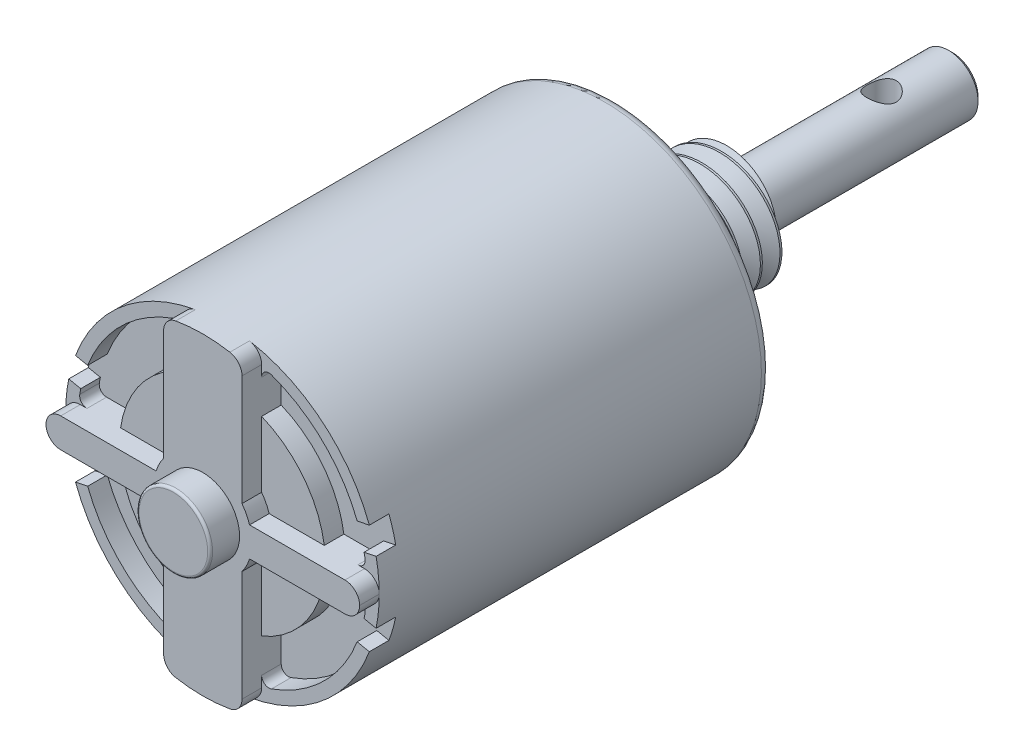
SolidWorks part; units mm, degrees
material "PET"
ref_plane "Front Plane" through (0, 0, 0) normal (0, 0, 1) x (1, 0, 0)
ref_plane "Top Plane" through (0, 0, 0) normal (0, 1, 0) x (1, 0, 0)
ref_plane "Right Plane" through (0, 0, 0) normal (1, 0, 0) x (0, 0, -1)
sketch "Sketch1" plane through (0, 0, 0) normal (0, 0, 1) x (1, 0, 0)
  circle A0 centre (0, 0) radius 16
  dimension "D1" = 32
extrude "Boss-Extrude1" add sketch "Sketch1" along normal blind 21
sketch "Sketch2" plane through (0, 0, 21) normal (0, 0, 1) x (1, 0, 0)
  circle A0 centre (0, 0) radius 16
  dimension "D1" = 32
extrude "Boss-Extrude2" add sketch "Sketch2" along normal blind 19
sketch "Sketch3" plane through (0, 0, 40) normal (0, 0, 1) x (1, 0, 0)
  line L0 (-4, -15.4919) -> (-4, -1.5)
  line L4 (4, -15.4919) -> (4, -1.5)
  line L5 (4, -1.5) -> (15.9295, -1.5)
  line L6 (-15.9295, -1.5) -> (-4, -1.5)
  line L7 (-15.9295, 1.5) -> (-4, 1.5)
  line L8 (4, 1.5) -> (4, 15.4919)
  line L9 (-4, 1.5) -> (-4, 15.4919)
  line L12 (4, 1.5) -> (15.9295, 1.5)
  arc A0 (-15.9295, 1.5) -> (-15.9295, -1.5) centre (0, 0) ccw
  arc A2 (4, 15.4919) -> (-4, 15.4919) centre (0, 0) ccw
  arc A3 (15.9295, -1.5) -> (15.9295, 1.5) centre (0, 0) ccw
  arc A4 (-4, -15.4919) -> (4, -15.4919) centre (0, 0) ccw
  point P10 (-20.25, 0)
  point P11 (20.25, 0)
  point P15 (-20.25, -1.5)
  point P16 (20.25, -1.5)
  point P17 (-20.25, 1.5)
  point P18 (20.25, 1.5)
extrude "Boss-Extrude3" add sketch "Sketch3" along normal blind 2
ref_plane "Plane1" through (0, 0, 40) normal (0, 0, 1) x (1, 0, 0)
sketch "Sketch4" plane through (0, 0, 40) normal (0, 0, 1) x (1, 0, 0)
  line L0 (10.3923, 1.5) -> (13.818, 1.5)
  line L1 (0, 0) -> (5.4478, 0) construction
  line L2 (0, 0) -> (0, -4.6183) construction
  line L3 (4, 13.1696) -> (4, 9.7082)
  line L4 (14.9913, -5.5911) -> (13.7497, -5.3393)
  line L5 (14.4557, -2.9316) -> (15.6808, -3.1801)
  line L6 (14.4557, 2.9316) -> (15.6808, 3.1801)
  line L7 (4, -13.1696) -> (4, -9.7082)
  line L8 (14.9913, 5.5911) -> (13.7497, 5.3393)
  line L9 (10.3923, -1.5) -> (13.818, -1.5)
  line L10 (-14.9913, 5.5911) -> (-13.7497, 5.3393)
  line L11 (-14.4557, 2.9316) -> (-15.6808, 3.1801)
  line L12 (-14.4557, -2.9316) -> (-15.6808, -3.1801)
  line L13 (-14.9913, -5.5911) -> (-13.7497, -5.3393)
  line L14 (-10.3923, -1.5) -> (-13.818, -1.5)
  line L15 (-4, -13.1696) -> (-4, -9.7082)
  line L16 (-4, 13.1696) -> (-4, 9.7082)
  line L17 (-10.3923, 1.5) -> (-13.818, 1.5)
  arc A0 (10.3923, 1.5) -> (4, 9.7082) centre (0, 0) ccw
  arc A1 (14.5583, 2.3705) -> (14.4557, 2.9316) centre (0, 0) ccw
  arc A3 (14.5583, 2.3705) -> (13.818, 1.5) centre (13.818, 2.25) cw
  arc A4 (5.0045, 13.8751) -> (4, 13.1696) centre (4.75, 13.1696) ccw
  arc A5 (15.9295, 1.5) -> (4, 15.4919) centre (0, 0) ccw construction
  arc A6 (13.7497, 5.3393) -> (5.0045, 13.8751) centre (0, 0) ccw
  arc A7 (15.6808, 3.1801) -> (14.9913, 5.5911) centre (0, 0) ccw
  arc A8 (5.0045, -13.8751) -> (4, -13.1696) centre (4.75, -13.1696) cw
  arc A9 (15.6808, -3.1801) -> (14.9913, -5.5911) centre (0, 0) cw
  arc A10 (13.7497, -5.3393) -> (5.0045, -13.8751) centre (0, 0) cw
  arc A11 (14.5583, -2.3705) -> (13.818, -1.5) centre (13.818, -2.25) ccw
  arc A12 (14.5583, -2.3705) -> (14.4557, -2.9316) centre (0, 0) cw
  arc A13 (10.3923, -1.5) -> (4, -9.7082) centre (0, 0) cw
  arc A14 (-14.5583, -2.3705) -> (-14.4557, -2.9316) centre (0, 0) ccw
  arc A15 (-14.5583, -2.3705) -> (-13.818, -1.5) centre (-13.818, -2.25) cw
  arc A16 (-15.6808, -3.1801) -> (-14.9913, -5.5911) centre (0, 0) ccw
  arc A17 (-15.6808, 3.1801) -> (-14.9913, 5.5911) centre (0, 0) cw
  arc A18 (-14.5583, 2.3705) -> (-13.818, 1.5) centre (-13.818, 2.25) ccw
  arc A19 (-14.5583, 2.3705) -> (-14.4557, 2.9316) centre (0, 0) cw
  arc A20 (-10.3923, -1.5) -> (-4, -9.7082) centre (0, 0) ccw
  arc A21 (-13.7497, -5.3393) -> (-5.0045, -13.8751) centre (0, 0) ccw
  arc A22 (-5.0045, -13.8751) -> (-4, -13.1696) centre (-4.75, -13.1696) ccw
  arc A23 (-13.7497, 5.3393) -> (-5.0045, 13.8751) centre (0, 0) cw
  arc A24 (-5.0045, 13.8751) -> (-4, 13.1696) centre (-4.75, 13.1696) cw
  arc A25 (-10.3923, 1.5) -> (-4, 9.7082) centre (0, 0) cw
  dimension "D1" = 1.25
  dimension "D2" = 4.25
  dimension "D3" = 0.75
  dimension "D5" = 1.25
extrude "Cut-Extrude1" cut sketch "Sketch4" against normal blind 2
sketch "Sketch5" plane through (0, 0, 42) normal (0, 0, 1) x (1, 0, 0)
  circle A0 centre (0, 0) radius 3.75
  dimension "D1" = 7.5
extrude "Boss-Extrude4" add sketch "Sketch5" along normal blind 3
fillet "Fillet1" radius 0.25 1 edges at (3.75, 0, 45)
fillet "Fillet2" radius 1.5 8 edges
ref_plane "Plane2" through (0, 0, 40) normal (0, 0, 1) x (1, 0, 0)
sketch "Sketch6" plane through (0, 0, 40) normal (0, 0, 1) x (1, 0, 0)
  circle A0 centre (0, 0) radius 5
  dimension "D1" = 10
extrude "Boss-Extrude5" add sketch "Sketch6" along normal blind 2
fillet "Fillet3" radius 1 1 edges at (16, 0, 0)
sketch "Sketch7" plane through (0, 0, 0) normal (0, 0, -1) x (-1, 0, 0)
  circle A0 centre (0, 0) radius 6
  dimension "D1" = 12
extrude "Boss-Extrude6" add sketch "Sketch7" along normal blind 12
sketch "Sketch8" plane through (0, 0, -12) normal (0, 0, -1) x (-1, 0, 0)
  circle A0 centre (0, 0) radius 3
  dimension "D1" = 6
extrude "Boss-Extrude7" add sketch "Sketch8" along normal blind 22.5
sketch "Sketch9" plane through (0, 0, 0) normal (0, 1, 0) x (1, 0, 0)
  line L0 (0, 34.5) -> (0, 27.25) construction
  line L1 (3, 34.5) -> (-3, 34.5) construction
  circle A0 centre (0, 27.25) radius 1.5
  dimension "D2" = 3
  dimension "D1" = 7.25
extrude "Cut-Extrude2" cut sketch "Sketch9" against normal blind 10 and the other way blind 10
chamfer "Chamfer1" distance 0.4 angle 45 1 edges at (-3, 0, -34.5)
ref_plane "Plane3" through (0, 0, -15) normal (0, 0, -1) x (-1, 0, 0)
sketch "Sketch10" plane through (0, 0, -15) normal (0, 0, -1) x (-1, 0, 0)
  circle A0 centre (0, 0) radius 6
curve "Helix/Spiral1" pitch 2 height 18 radius 6 centre (0, 0, -15) axis (0, 0, 1) start towards (1, 0, 0)
ref_plane "Plane4" through (0, 0, 0) normal (0, 1, 0) x (1, 0, 0)
sketch "Sketch11" plane through (0, 0, 0) normal (0, 1, 0) x (1, 0, 0)
  line L3 (6, 0) -> (6, 12) construction
  line L7 (4.4412, 15.9831) -> (6, 15.0831)
  line L8 (6, 15.0831) -> (6, 16.8831)
  line L9 (6, 16.8831) -> (4.4412, 15.9831)
  circle A1 centre (5.4804, 15.9831) radius 0.5196 construction
  dimension "D3" = 1.8
sweep "Cut-Sweep5" cut profiles "Sketch11" path "Helix/Spiral1" align with end faces yes
sketch "Sketch12" plane through (0, 0, 0) normal (0, 0, -1) x (-1, 0, 0)
  circle A0 centre (0, 0) radius 6
extrude "Boss-Extrude8" add sketch "Sketch12" against normal blind 4
